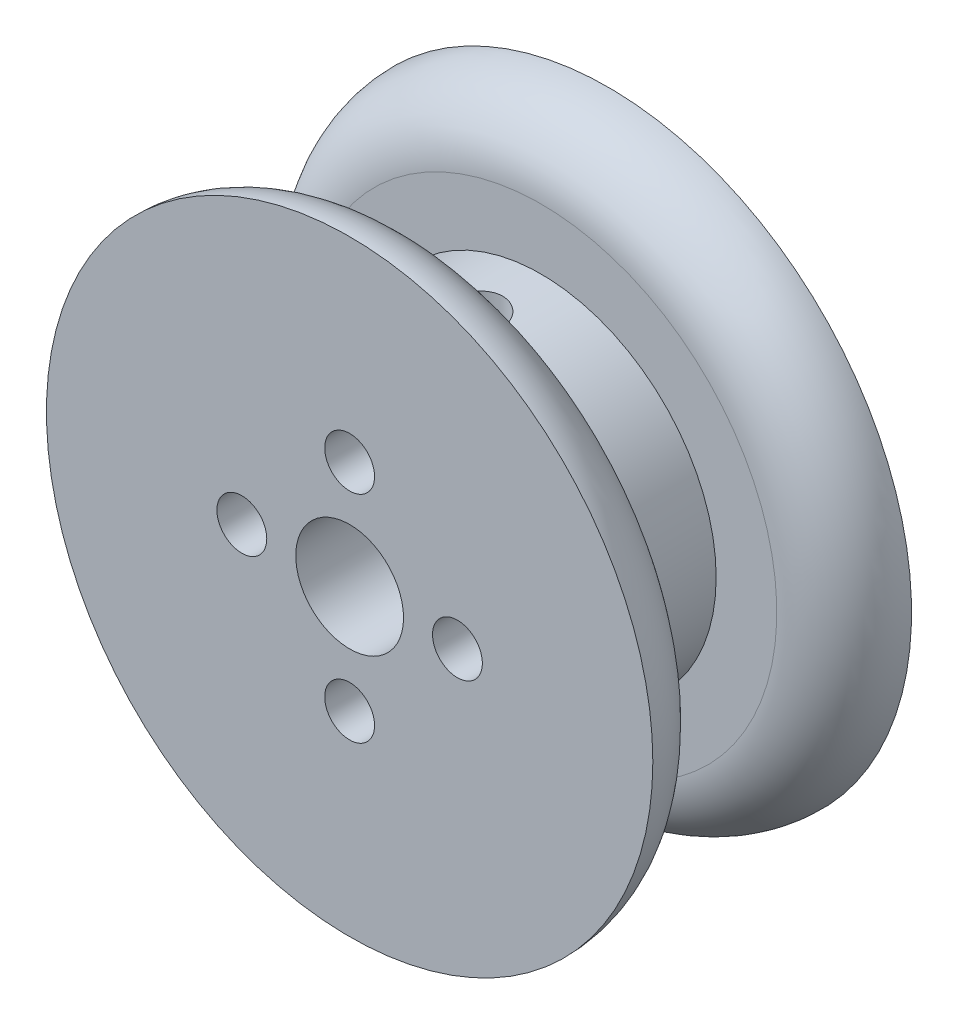
SolidWorks part; units mm, degrees
ref_plane "Front Plane" through (0, 0, 0) normal (0, 0, 1) x (1, 0, 0)
ref_plane "Top Plane" through (0, 0, 0) normal (0, 1, 0) x (1, 0, 0)
ref_plane "Right Plane" through (0, 0, 0) normal (1, 0, 0) x (0, 0, -1)
sketch "Sketch1" plane through (0, 0, 0) normal (0, 0, 1) x (1, 0, 0)
  circle A5 centre (0, 0) radius 22.5
  dimension "D1" = 45
extrude "Boss-Extrude1" add sketch "Sketch1" along normal blind 5
sketch "Sketch2" plane through (0, 0, 0) normal (0, 0, 1) x (1, 0, 0)
  circle A0 centre (0, 0) radius 13
  dimension "D1" = 26
extrude "Boss-Extrude2" add sketch "Sketch2" against normal blind 9.2
sketch "Sketch5" plane through (0, 0, -9.2) normal (0, 0, -1) x (-1, 0, 0)
  circle A2 centre (0, 0) radius 22.5
  circle A3 centre (0, 0) radius 22.5
  dimension "D1" = 0
extrude "Boss-Extrude4" add sketch "Sketch5" along normal blind 5
sketch "Sketch6" plane through (0, 0, 5) normal (0, 0, 1) x (1, 0, 0)
  line L0 (0, 0) -> (0, 8) construction
  circle A0 centre (0, 0) radius 4
  circle A1 centre (0, 8) radius 1.85
  circle A2 centre (8, 0) radius 1.85
  circle A3 centre (0, -8) radius 1.85
  circle A4 centre (-8, 0) radius 1.85
  point P14 (0, 0)
  dimension "D1" = 8
  dimension "D3" = 3.7
  dimension "D2" = 8
  dimension "D4" = 4
extrude "Cut-Extrude1" cut sketch "Sketch6" against normal through all
fillet "Fillet1" radius 5 2 edges at (22.5, 0, 0) (-22.5, 0, -9.2)
ref_plane "Plane1" through (0, 0, -14.2) normal (0, 0, -1) x (-1, 0, 0)
sketch "Sketch8" plane through (0, 0, 0) normal (0, 1, 0) x (1, 0, 0)
  line L0 (-4, -5) -> (4, -5) construction
  circle A0 centre (0, 4.5) radius 1.85
  dimension "D1" = 3.7
  dimension "D2" = 9.5
extrude "Cut-Extrude2" cut sketch "Sketch8" against normal blind 26 and the other way blind 26
